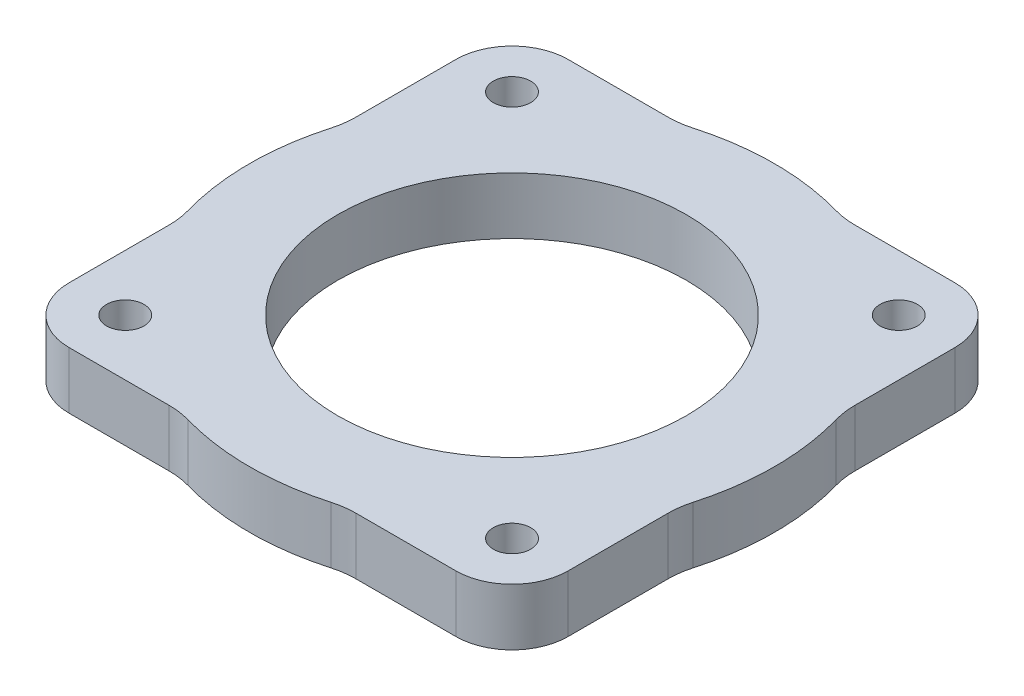
SolidWorks part; units mm, degrees
ref_plane "Front Plane" through (0, 0, 0) normal (0, 0, 1) x (1, 0, 0)
ref_plane "Top Plane" through (0, 0, 0) normal (0, 1, 0) x (1, 0, 0)
ref_plane "Right Plane" through (0, 0, 0) normal (1, 0, 0) x (0, 0, -1)
sketch "Sketch1" plane through (0, 0, 0) normal (0, 1, 0) x (1, 0, 0)
  line L0 (0, 43.6291) -> (0, 56.3563)
  line L1 (7.1437, 0) -> (19.8709, 0)
  line L2 (0, 7.1437) -> (0, 19.8709)
  line L3 (7.1437, 63.5) -> (19.8709, 63.5)
  line L4 (63.5, 7.1437) -> (63.5, 19.8709)
  line L5 (43.6291, 63.5) -> (56.3563, 63.5)
  line L6 (63.5, 43.6291) -> (63.5, 56.3563)
  line L7 (43.6291, 0) -> (56.3563, 0)
  circle A0 centre (31.75, 31.75) radius 22.1742
  circle A1 centre (56.3563, 56.3563) radius 2.3812
  circle A2 centre (56.3563, 7.1437) radius 2.3812
  circle A3 centre (7.1437, 7.1437) radius 2.3812
  circle A4 centre (7.1437, 56.3563) radius 2.3812
  arc A7 (7.1437, 63.5) -> (0, 56.3563) centre (7.1437, 56.3563) ccw
  arc A8 (56.3563, 0) -> (63.5, 7.1437) centre (56.3563, 7.1437) ccw
  arc A9 (0, 7.1437) -> (7.1437, 0) centre (7.1437, 7.1437) ccw
  arc A10 (63.5, 56.3563) -> (56.3563, 63.5) centre (56.3563, 56.3563) ccw
  arc A11 (-0.3851, 40.8585) -> (-0.3851, 22.6415) centre (31.75, 31.75) ccw
  arc A12 (22.6415, -0.3851) -> (40.8585, -0.3851) centre (31.75, 31.75) ccw
  arc A13 (40.8585, 63.8851) -> (22.6415, 63.8851) centre (31.75, 31.75) ccw
  arc A14 (63.8851, 22.6415) -> (63.8851, 40.8585) centre (31.75, 31.75) ccw
  arc A15 (63.8851, 40.8585) -> (63.5, 43.6291) centre (73.66, 43.6291) cw
  arc A16 (63.5, 19.8709) -> (63.8851, 22.6415) centre (73.66, 19.8709) cw
  arc A17 (40.8585, -0.3851) -> (43.6291, 0) centre (43.6291, -10.16) cw
  arc A18 (22.6415, -0.3851) -> (19.8709, 0) centre (19.8709, -10.16) ccw
  arc A19 (0, 19.8709) -> (-0.3851, 22.6415) centre (-10.16, 19.8709) ccw
  arc A20 (-0.3851, 40.8585) -> (0, 43.6291) centre (-10.16, 43.6291) ccw
  arc A21 (22.6415, 63.8851) -> (19.8709, 63.5) centre (19.8709, 73.66) cw
  arc A22 (43.6291, 63.5) -> (40.8585, 63.8851) centre (43.6291, 73.66) cw
  point P16 (63.5, 42.1213)
  point P31 (63.5, 21.3787)
  point P34 (42.1213, 0)
  point P41 (0, 42.1213)
  point P46 (42.1213, 63.5)
  point P47 (0, 0)
  point P48 (0, 0)
  point P49 (0, 0)
  dimension "D3" = 44.3484
  dimension "D6" = 4.7625
  dimension "D7" = 4.7625
  dimension "D8" = 4.7625
  dimension "D9" = 4.7625
  dimension "D10" = 7.1437
  dimension "D11" = 7.1437
  dimension "D12" = 7.1437
  dimension "D13" = 7.1437
  dimension "D14" = 7.1437
  dimension "D15" = 7.1437
  dimension "D16" = 7.1437
  dimension "D17" = 7.1437
  dimension "D18" = 49.2125
  dimension "D2" = 10.16
  dimension "D19" = 11.2268
  dimension "D4" = 31.75
  dimension "D5" = 31.75
extrude "Boss-Extrude1" add sketch "Sketch1" against normal blind 7.239
